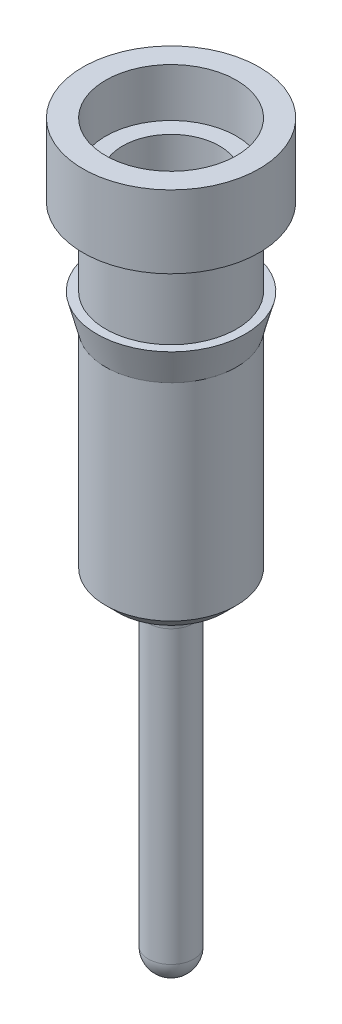
SolidWorks part; units mm, degrees
ref_plane "Front Plane" through (0, 0, 0) normal (0, 0, 1) x (1, 0, 0)
ref_plane "Top Plane" through (0, 0, 0) normal (0, 1, 0) x (1, 0, 0)
ref_plane "Right Plane" through (0, 0, 0) normal (1, 0, 0) x (0, 0, -1)
sketch "Sketch1" plane through (0, 0, 0) normal (0, 0, 1) x (1, 0, 0)
  line L0 (0, 0) -> (0, 3.75)
  line L1 (0, 3.75) -> (0.5, 3.75)
  line L2 (0.5, 3.75) -> (0.5, 6.9)
  line L3 (0.675, 7.4) -> (0.91, 7.4)
  line L4 (0.91, 7.4) -> (0.91, 6.65)
  line L5 (0.91, 6.65) -> (0.675, 6.65)
  line L6 (0.675, 6.65) -> (0.675, 5.85)
  line L7 (0.675, 5.85) -> (0.765, 5.85)
  line L8 (0.765, 5.85) -> (0.675, 5.51)
  line L9 (0.675, 5.51) -> (0.675, 3.38)
  line L10 (0.675, 3.38) -> (0.545, 3.25)
  line L11 (0.545, 3.25) -> (0.235, 3.25)
  line L12 (0.235, 3.25) -> (0.235, 0)
  line L13 (0.235, 0) -> (0, 0)
  line L14 (0.5, 6.9) -> (0.675, 6.9)
  line L15 (0.675, 6.9) -> (0.675, 7.4)
  dimension "D1" = 0.235
  dimension "D2" = 0.675
  dimension "D3" = 0.765
  dimension "D4" = 0.91
  dimension "D5" = 7.4
  dimension "D6" = 0.13
  dimension "D7" = 2.13
  dimension "D8" = 0.34
  dimension "D9" = 0.8
  dimension "D10" = 0.75
  dimension "D11" = 0.5
  dimension "D12" = 0.13
  dimension "D13" = 0.5
  dimension "D14" = 0.675
  dimension "D15" = 0.5
revolve "Revolve1" add sketch "Sketch1" angle 360 about L0
dome "Dome1" faces to dome 1 distance 0.235 reverse direction no elliptical dome no face at (0, 3.75, -0.5) parameters "D1"=0.235
dome "Dome2" faces to dome 1 distance 0.235 reverse direction no elliptical dome no face at (0, 0, -0.235) parameters "D1"=0.235
fillet "Fillet1" radius 0.25 1 edges at (0, 3.25, -0.235)
